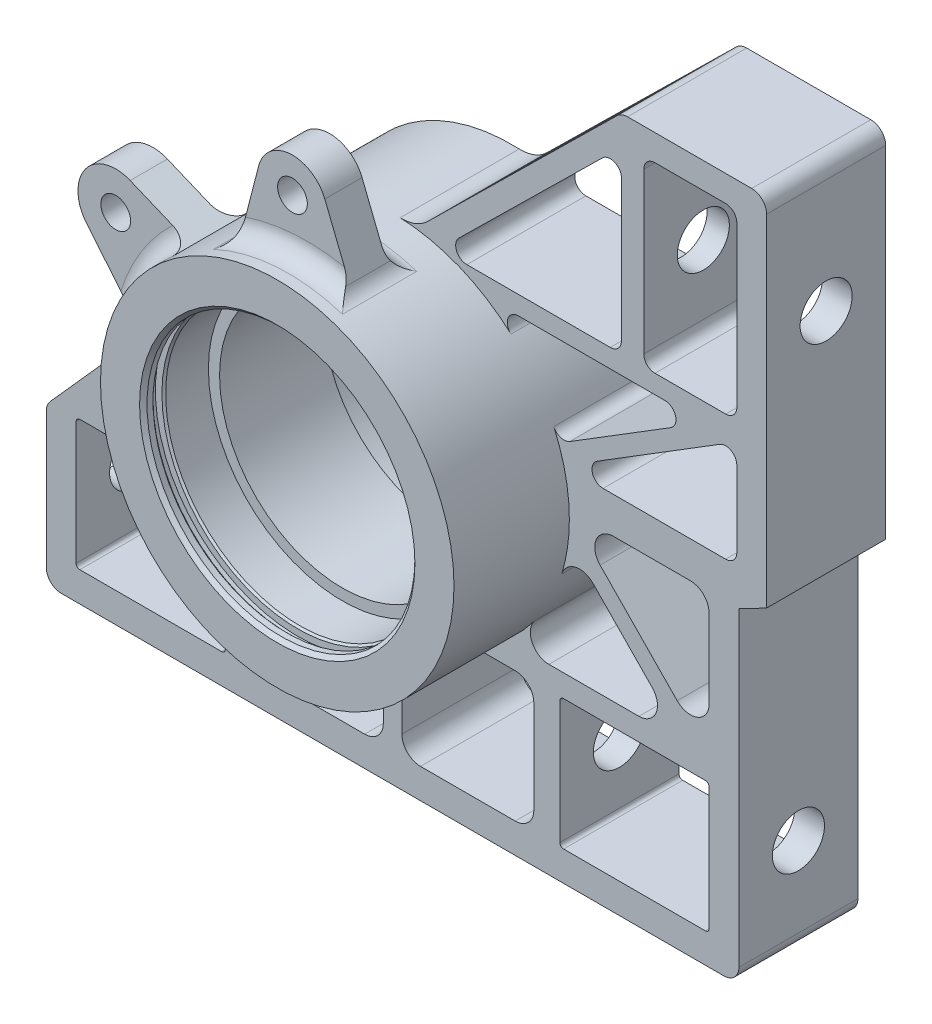
SolidWorks part; units mm, degrees
material "7075-T6 (SN)"
ref_plane "Front Plane" through (0, 0, 0) normal (0, 0, 1) x (1, 0, 0)
ref_plane "Top Plane" through (0, 0, 0) normal (0, 1, 0) x (1, 0, 0)
ref_plane "Right Plane" through (0, 0, 0) normal (1, 0, 0) x (0, 0, -1)
sketch "Sketch1" plane through (0, 0, 0) normal (0, 0, 1) x (1, 0, 0)
  circle A0 centre (0, 0) radius 36
  circle A1 centre (0, 0) radius 47.5
  dimension "D1" = 72
  dimension "D2" = 95
extrude "Boss-Extrude1" add sketch "Sketch1" along normal blind 60 and the other way blind 3
sketch "Sketch2" plane through (0, 0, -3) normal (0, 0, -1) x (-1, 0, 0)
  line L0 (0, 0) -> (0, -85.5) construction
  line L1 (-89.05, -85.5) -> (89.05, -85.5)
  line L2 (93.05, -81.5) -> (93.05, -45.0252)
  line L4 (-63.1377, 101.5) -> (-96.5, 101.5)
  line L6 (-65, -60) -> (65, -60) construction
  line L7 (-65, -60) -> (-65, 70) construction
  line L8 (-65, 70) -> (-80, 70) construction
  line L9 (-84.05, -77.5) -> (-45.95, -77.5)
  line L10 (-85.05, -76.5) -> (-85.05, -43.5)
  line L11 (-84.05, -42.5) -> (-45.95, -42.5)
  line L12 (-44.95, -76.5) -> (-44.95, -43.5)
  line L13 (-85.05, -77.5) -> (-44.95, -42.5) construction
  line L14 (-85.05, -42.5) -> (-44.95, -77.5) construction
  line L15 (45.95, -77.5) -> (84.05, -77.5)
  line L16 (44.95, -76.5) -> (44.95, -43.5)
  line L17 (45.95, -42.5) -> (84.05, -42.5)
  line L18 (85.05, -76.5) -> (85.05, -43.5)
  line L19 (44.95, -77.5) -> (85.05, -42.5) construction
  line L20 (44.95, -42.5) -> (85.05, -77.5) construction
  line L25 (-100.5, 97.5) -> (-100.5, 5.8481)
  line L26 (-89.5, 94.5) -> (-70.5, 94.5)
  line L27 (-92.5, 91.5) -> (-92.5, 48.5)
  line L28 (-89.5, 45.5) -> (-70.5, 45.5)
  line L29 (-67.5, 91.5) -> (-67.5, 48.5)
  line L30 (-92.5, 94.5) -> (-67.5, 45.5) construction
  line L31 (-92.5, 45.5) -> (-67.5, 94.5) construction
  line L32 (-93.05, -81.5) -> (-93.05, 1.9641)
  line L33 (-93.05, 1.9641) -> (-100.5, 5.8481)
  line L34 (92.0346, -42.362) -> (46.7544, 8.3829)
  line L35 (-60.3325, 100.3515) -> (-6.1946, 47.0943)
  line L36 (-61.5, 86.425) -> (-61.5, 48.5)
  line L37 (-58.5, 45.5) -> (-19.9478, 45.5)
  line L38 (-17.844, 50.6386) -> (-56.3961, 88.5636)
  line L39 (-92.5, 35.114) -> (-92.5, 14.7271)
  line L40 (-89.5, 11.7271) -> (-56.5736, 11.7271)
  line L41 (-54.9943, 17.2778) -> (-87.9207, 37.6647)
  line L42 (-74.7284, 34.9493) -> (-47.6317, 18.172)
  line L43 (-73.1491, 40.5) -> (-33.8231, 40.5)
  line L44 (-85.05, -3.0359) -> (-85.05, -24.2301)
  line L45 (-76.4741, -27.7248) -> (-55.7612, -6.5306)
  line L46 (-59.3371, 1.9641) -> (-80.05, 1.9641)
  line L47 (-69.757, -28.0053) -> (-53.8273, -11.7055)
  line L60 (-66.1811, -36.5) -> (-42, -36.5)
  line L68 (53.6007, -6.837) -> (75.599, -31.4902)
  line L69 (72.6144, -38.1534) -> (49.95, -38.1534)
  line L71 (44.95, -33.1534) -> (44.95, -15.3541)
  line L72 (-32.95, -77.5) -> (-7.5, -77.5)
  line L73 (-2.5, -72.5) -> (-2.5, -47.4342)
  line L74 (-37.95, -72.5) -> (-37.95, -47.5)
  line L75 (-32.95, -42.5) -> (-21.2132, -42.5)
  line L76 (2.5, -72.5) -> (2.5, -47.4342)
  line L77 (7.5, -77.5) -> (32.9501, -77.5)
  line L78 (37.95, -72.5331) -> (37.95, -28.5665)
  circle A0 centre (0, 0) radius 47.5 construction
  arc A1 (24.8193, 40.5) -> (-44.6143, 16.3038) centre (0, 0) ccw construction
  arc A2 (-31.8138, 35.2723) -> (-43.3166, 19.4916) centre (0, 0) ccw
  arc A3 (-46.0296, 11.7271) -> (-47.4974, 0.497) centre (0, 0) ccw construction
  arc A4 (-45.4656, -13.7526) -> (-38, -28.5) centre (0, 0) ccw
  arc A5 (-47.2398, -4.965) -> (-30.3974, -36.5) centre (0, 0) ccw construction
  circle A7 centre (0, 0) radius 47.5
  arc A9 (7.4649, -46.9098) -> (37.95, -28.5665) centre (0, 0) ccw construction
  arc A10 (44.3531, -17.0017) -> (46.9996, -6.8768) centre (0, 0) ccw
  arc A11 (43.2647, -19.6065) -> (46.6848, -8.7623) centre (0, 0) ccw construction
  arc A12 (-33.8144, -33.3592) -> (-11.3105, -46.1337) centre (0, 0) ccw
  arc A13 (-37.95, -28.5665) -> (-7.4649, -46.9098) centre (0, 0) ccw construction
  arc A16 (-45.95, -77.5) -> (-44.95, -76.5) centre (-45.95, -76.5) ccw
  arc A17 (-84.05, -77.5) -> (-85.05, -76.5) centre (-84.05, -76.5) cw
  arc A18 (-85.05, -43.5) -> (-84.05, -42.5) centre (-84.05, -43.5) cw
  arc A19 (-45.95, -42.5) -> (-44.95, -43.5) centre (-45.95, -43.5) cw
  arc A20 (45.95, -77.5) -> (44.95, -76.5) centre (45.95, -76.5) cw
  arc A21 (84.05, -77.5) -> (85.05, -76.5) centre (84.05, -76.5) ccw
  arc A22 (84.05, -42.5) -> (85.05, -43.5) centre (84.05, -43.5) cw
  arc A23 (44.95, -43.5) -> (45.95, -42.5) centre (45.95, -43.5) cw
  arc A24 (-70.5, 45.5) -> (-67.5, 48.5) centre (-70.5, 48.5) ccw
  arc A25 (-92.5, 48.5) -> (-89.5, 45.5) centre (-89.5, 48.5) ccw
  arc A26 (-89.5, 94.5) -> (-92.5, 91.5) centre (-89.5, 91.5) ccw
  arc A27 (-70.5, 94.5) -> (-67.5, 91.5) centre (-70.5, 91.5) cw
  arc A28 (-19.9478, 45.5) -> (-17.844, 50.6386) centre (-19.9478, 48.5) ccw
  arc A29 (-61.5, 48.5) -> (-58.5, 45.5) centre (-58.5, 48.5) ccw
  arc A30 (-61.5, 86.425) -> (-56.3961, 88.5636) centre (-58.5, 86.425) cw
  arc A31 (-47.6317, 18.172) -> (-43.3166, 19.4916) centre (-46.0524, 20.7226) ccw
  arc A32 (-74.7284, 34.9493) -> (-73.1491, 40.5) centre (-73.1491, 37.5) cw
  arc A33 (-33.8231, 40.5) -> (-31.8138, 35.2723) centre (-33.8231, 37.5) cw
  arc A34 (-92.5, 14.7271) -> (-89.5, 11.7271) centre (-89.5, 14.7271) ccw
  arc A35 (-56.5736, 11.7271) -> (-54.9943, 17.2778) centre (-56.5736, 14.7271) ccw
  arc A36 (-92.5, 35.114) -> (-87.9207, 37.6647) centre (-89.5, 35.114) cw
  arc A37 (-42, -36.5) -> (-38, -28.5) centre (-42, -31.5) ccw
  arc A38 (-53.8273, -11.7055) -> (-45.4656, -13.7526) centre (-50.2514, -15.2002) cw
  arc A39 (-69.757, -28.0053) -> (-66.1811, -36.5) centre (-66.1811, -31.5) ccw
  arc A40 (-85.05, -24.2301) -> (-76.4741, -27.7248) centre (-80.05, -24.2301) ccw
  arc A41 (-55.7612, -6.5306) -> (-59.3371, 1.9641) centre (-59.3371, -3.0359) ccw
  arc A42 (-85.05, -3.0359) -> (-80.05, 1.9641) centre (-80.05, -3.0359) cw
  arc A61 (89.05, -85.5) -> (93.05, -81.5) centre (89.05, -81.5) ccw
  arc A62 (-89.05, -85.5) -> (-93.05, -81.5) centre (-89.05, -81.5) cw
  arc A64 (93.05, -45.0252) -> (92.0346, -42.362) centre (89.05, -45.0252) ccw
  arc A65 (-60.3325, 100.3515) -> (-63.1377, 101.5) centre (-63.1377, 97.5) ccw
  arc A66 (-96.5, 101.5) -> (-100.5, 97.5) centre (-96.5, 97.5) ccw
  arc A67 (49.95, -38.1534) -> (44.95, -33.1534) centre (49.95, -33.1534) cw
  arc A69 (32.9501, -77.5) -> (37.95, -72.5331) centre (32.9501, -72.5) ccw
  arc A70 (2.5, -72.5) -> (7.5, -77.5) centre (7.5, -72.5) ccw
  arc A71 (-7.5, -77.5) -> (-2.5, -72.5) centre (-7.5, -72.5) ccw
  arc A72 (-32.95, -77.5) -> (-37.95, -72.5) centre (-32.95, -72.5) cw
  arc A73 (-37.95, -47.5) -> (-32.95, -42.5) centre (-32.95, -47.5) cw
  arc A74 (53.6007, -6.837) -> (46.6848, -8.7623) centre (50.6162, -9.5002) ccw
  arc A75 (75.599, -31.4902) -> (72.6144, -38.1534) centre (72.6144, -34.1534) cw
  point P6 (0, -85.5)
  point P125 (-92.5, 40.5)
  point P136 (-85.05, -36.5)
  point P139 (-47.4594, 1.9641)
  point P150 (2.5, -77.5)
  point P154 (-2.5, -77.5)
  point P163 (47.5, 0)
  point P164 (85.05, -44.3653)
  point P165 (33.4574, -33.7173)
  point P197 (93.05, -85.5)
  point P203 (93.05, -43.5)
  point P206 (-61.5, 101.5)
  point P209 (-100.5, 101.5)
  circle M4 centre (0, 0) radius 47.5
  dimension "D16" = 95
  dimension "D18" = 5
  dimension "D25" = 1
  dimension "D26" = 1
  dimension "D27" = 3
  dimension "D28" = 3
  dimension "D29" = 3
  dimension "D30" = 3
  dimension "D31" = 5
  dimension "D35" = 4
  dimension "D36" = 4
  dimension "D7" = 7
  dimension "D5" = 7
  dimension "D20" = 47.5
  dimension "D21" = 5
  dimension "D22" = 4
  dimension "D1" = 130
  dimension "D3" = 130
  dimension "D4" = 33
  dimension "D6" = 40.1
  dimension "D8" = 35
  dimension "D9" = 7
  dimension "D10" = 15
  dimension "D11" = 25
  dimension "D12" = 49
  dimension "D13" = 8
  dimension "8" = 8
  dimension "D14" = 8
  dimension "D15" = 39
  dimension "D17" = 73.5289
  dimension "D19" = 6
  dimension "D23" = 42
  dimension "D24" = 0
  dimension "D37" = 5
  dimension "D38" = 5
extrude "Boss-Extrude2" add sketch "Sketch2" against normal blind 32 contours L4 A66 L25 L33 L32 A62 L1 A61 L2 A64 L34 L35 A65 A10 L44 A42 L46 A41 L45 A40 L39 A36 L41 A35 M4 region at (89.9754, -82.4254, -3)
sketch3d "3DSketch1" plane through (0, 0, 0) normal (0, 0, 1) x (1, 0, 0)
  dimension "D1" = 10
sketch "Sketch3" plane through (0, 0, 50) normal (0, 0, 1) x (1, 0, 0)
  line L0 (-4.7305, 61.146) -> (-51.4002, 33.455) construction
  line L1 (-28.0653, 47.3005) -> (0, 0) construction
  line L2 (4.6933, 64.9164) -> (12.5436, 45.2952)
  line L3 (-4.7305, 61.146) -> (0, 0) construction
  line L4 (-14.622, 63.4221) -> (-19.361, 42.827)
  line L5 (-28.3103, 37.517) -> (-48.6575, 43.2274)
  line L6 (-51.4002, 33.455) -> (0, 0) construction
  line L7 (-45.7664, 10.6975) -> (-59.2255, 26.9908)
  circle A0 centre (0, 0) radius 61.3287 construction
  circle A1 centre (-4.7305, 61.146) radius 3.5
  circle A2 centre (-51.4002, 33.455) radius 3.5
  circle A3 centre (-4.7305, 61.146) radius 10.15
  circle A4 centre (-51.4002, 33.455) radius 10.15
  circle A5 centre (0, 0) radius 47
  point P7 (-28.0653, 47.3005)
  dimension "D1" = 55
  dimension "D2" = 20.3
  dimension "D3" = 7
  dimension "D6" = 20.3
  dimension "D8" = 16
  dimension "D9" = 94
  dimension "D4" = 54.2665
  dimension "D5" = 54.2665
  dimension "D7" = 16
fillet "Fillet4" radius 10 1 edges at (6.1946, 47.0943, 13)
sketch "Sketch4" plane through (100.5, 0, 0) normal (1, 0, 0) x (0, 0, -1)
  line L0 (-13, 94.5) -> (-13, 45.5) construction
  line L2 (-29, 94.5) -> (3, 94.5) construction
  line L3 (-29, 45.5) -> (3, 45.5) construction
  line L4 (-29, 94.5) -> (3, 94.5)
  line L5 (-29, 45.5) -> (3, 45.5)
  circle A1 centre (-13, 67) radius 7
  point P4 (-13, 70)
  dimension "D1" = 14
  dimension "D2" = 3
extrude "Cut-Extrude1" cut sketch "Sketch4" against normal up to surface (39 mm away) contours L0 A1 | A1 L0 region at (100.5, 67, 10.0291) region at (100.5, 67, 15.9709) up to face at (61.5, 67.4625, 13)
sketch "Sketch5" plane through (93.05, 0, 0) normal (1, 0, 0) x (0, 0, -1)
  line L0 (-29, -77.5) -> (3, -77.5) construction
  line L1 (-29, -42.5) -> (3, -42.5) construction
  line L2 (-29, -77.5) -> (3, -77.5)
  line L3 (-29, -42.5) -> (3, -42.5)
  line L4 (-13, -42.5) -> (-13, -77.5) construction
  circle A0 centre (-13, -60) radius 7
  dimension "D1" = 14
extrude "Cut-Extrude2" cut sketch "Sketch5" against normal blind 64 contours L4 A0 | A0 L4 region at (93.05, -60, 10.0291) region at (93.05, -60, 15.9709)
mirror "Mirror1" about plane through (0, 0, 0) normal (1, 0, 0) of "Cut-Extrude2"
ref_plane "Plane1" through (0, 0, 28.5) normal (0, 0, -1) x (-1, 0, 0)
sketch "Sketch6" plane through (0, 0, 28.5) normal (0, 0, -1) x (-1, 0, 0)
  circle A0 centre (0, 0) radius 36
  circle A1 centre (0, 0) radius 33
  dimension "D1" = 66
extrude "Boss-Extrude4" add sketch "Sketch6" along normal blind 14 and the other way blind 14
fillet "Fillet5" radius 4 3 edges at (2.5, -47.4342, 13) (-2.5, -47.4342, 13) (-37.95, -28.5665, 13)
ref_plane "Plane2" through (0, 0, 52) normal (0, 0, 1) x (1, 0, 0)
sketch "Sketch8" plane through (0, 0, 52) normal (0, 0, 1) x (1, 0, 0)
  line L0 (-3.9095, 61.2013) -> (-51.3974, 33.4542) construction
  line L1 (-27.6534, 47.3277) -> (0, 0) construction
  line L2 (4.7875, 64.6809) -> (12.5436, 45.2952)
  line L3 (-3.9095, 61.2013) -> (0, 0) construction
  line L4 (-12.9785, 63.546) -> (-18.205, 43.331)
  line L6 (-51.3974, 33.4542) -> (0, 0) construction
  line L7 (-45.7661, 10.6988) -> (-59.223, 26.9902)
  line L8 (-30.4779, 35.7784) -> (-48.0729, 43.0634)
  line L9 (-48.0729, 43.0634) -> (-48.6548, 43.2267)
  circle A0 centre (0, 0) radius 61.326 construction
  circle A1 centre (-3.9095, 61.2013) radius 4
  circle A2 centre (-51.3974, 33.4542) radius 4
  circle A3 centre (-3.9095, 61.2013) radius 9.3672
  circle A4 centre (-51.3974, 33.4542) radius 10.15
  circle A5 centre (0, 0) radius 47
  point P6 (-27.6534, 47.3277)
  point P15 (0, 0)
  point P20 (0, 0)
  point P21 (0, 0)
  point P22 (0, 0)
  dimension "D2" = 8
  dimension "D3" = 8
  dimension "D1" = 55
extrude "Boss-Extrude6" add sketch "Sketch8" against normal blind 10 contours A5 A4 L7 | A4 A2 | A5 L2 A3 L4 | A3 A1 region at (-3.242, 50.7524, 52) region at (5.0285, 62.9229, 52) region at (-43.203, 26.4175, 52) region at (-59.6635, 38.8346, 52)
fillet "Fillet12" radius 5 7 edges at (-3.0281, 47.4034, 42) (12.3109, 45.8769, 47) (-3.0281, 47.4034, 52) (-18.0482, 43.9376, 47) (-40.526, 24.7768, 42) (-40.526, 24.7768, 52) (-46.1651, 11.1819, 47)
ref_plane "Plane3" through (0, 0, 86.5) normal (0, 0, 1) x (1, 0, 0)
mirror "Mirror2" about plane through (0, 0, 86.5) normal (0, 0, 1) of bodies 112
delete or keep bodies "Body-Delete/Keep 1" type delete bodies bodies 113
ref_plane "Plane4" through (0, 0, 0) normal (0, 0, -1) x (-1, 0, 0)
sketch "Sketch9" plane through (0, 0, 0) normal (0, 0, -1) x (-1, 0, 0)
  circle A0 centre (0, 0) radius 36
  circle A1 centre (0, 0) radius 38.25
  dimension "D1" = 76.5
extrude "Cut-Extrude3" cut sketch "Sketch9" against normal blind 2.4
chamfer "Chamfer1" distance 0.5 angle 45 1 edges at (-36, 0, 0)
chamfer "Chamfer2" distance 1 angle 45 1 edges at (36, 0, -3)
chamfer "Chamfer3" distance 0.5 angle 45 1 edges at (-36, 0, 2.4)
ref_plane "Plane5" through (0, 0, 56.9) normal (0, 0, 1) x (1, 0, 0)
sketch "Sketch10" plane through (0, 0, 56.9) normal (0, 0, 1) x (1, 0, 0)
  circle A0 centre (0, 0) radius 36
  circle A1 centre (0, 0) radius 38.25
extrude "Cut-Extrude4" cut sketch "Sketch10" against normal blind 2.4
chamfer "Chamfer4" distance 0.5 angle 45 2 edges at (36, 0, 56.9) (36, 0, 54.5)
chamfer "Chamfer5" distance 1 angle 45 1 edges at (36, 0, 60)
